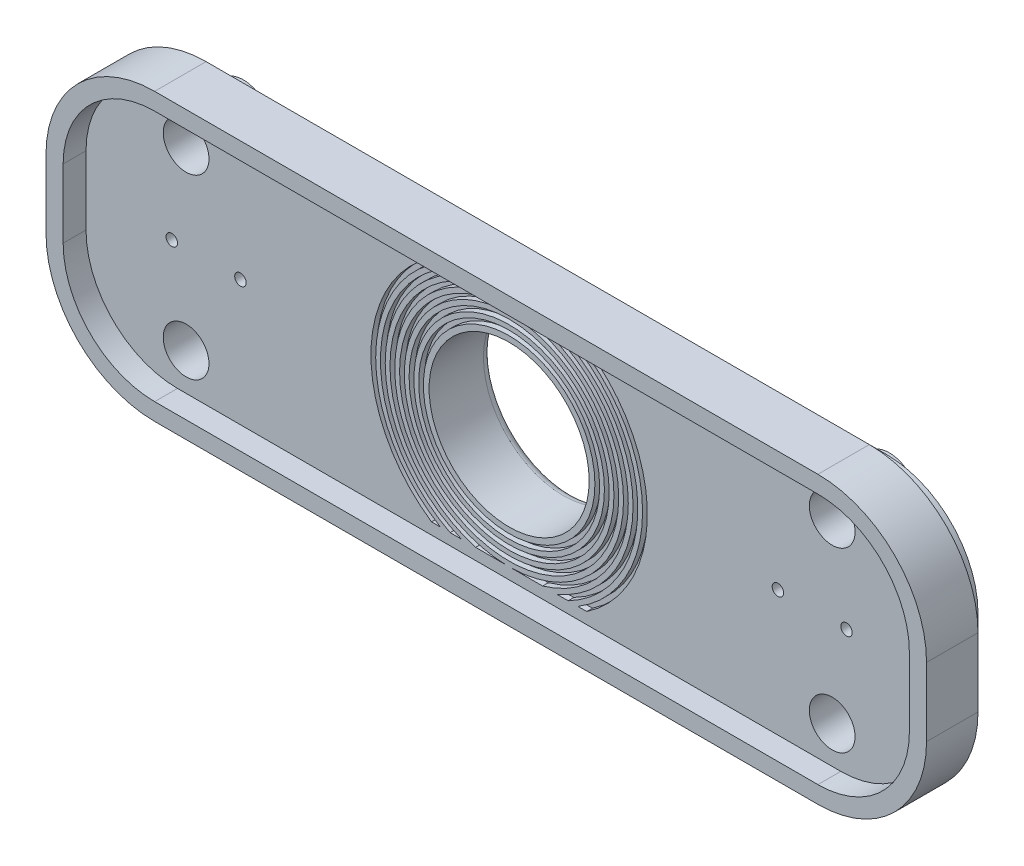
SolidWorks part; units mm, degrees
ref_plane "Front Plane" through (0, 0, 0) normal (0, 0, 1) x (1, 0, 0)
ref_plane "Top Plane" through (0, 0, 0) normal (0, 1, 0) x (1, 0, 0)
ref_plane "Right Plane" through (0, 0, 0) normal (1, 0, 0) x (0, 0, -1)
sketch "Sketch1" plane through (0, 0, 0) normal (0, 0, 1) x (1, 0, 0)
  line L0 (-29, 12.5) -> (29, 12.5)
  line L1 (-29, 11) -> (29, 11)
  line L2 (-37, 3) -> (-37, -3)
  line L3 (-29, -11) -> (29, -11)
  line L4 (37, 3) -> (37, -3)
  line L5 (38.5, 3) -> (38.5, -3)
  line L6 (-29, -12.5) -> (29, -12.5)
  line L7 (-38.5, 3) -> (-38.5, -3)
  arc A0 (29, -11) -> (37, -3) centre (29, -3) ccw
  arc A1 (29, 11) -> (37, 3) centre (29, 3) cw
  arc A2 (-37, -3) -> (-29, -11) centre (-29, -3) ccw
  arc A3 (-29, 11) -> (-37, 3) centre (-29, 3) ccw
  arc A4 (29, 12.5) -> (38.5, 3) centre (29, 3) cw
  arc A5 (29, -12.5) -> (38.5, -3) centre (29, -3) ccw
  arc A6 (-38.5, -3) -> (-29, -12.5) centre (-29, -3) ccw
  arc A7 (-29, 12.5) -> (-38.5, 3) centre (-29, 3) ccw
  point P4 (0, 11)
  point P6 (37, 0)
  point P9 (37, -11)
  point P12 (37, 11)
  dimension "D3" = 8
  dimension "D1" = 74
  dimension "D2" = 22
  dimension "D4" = 1.5
extrude "Boss-Extrude1" add sketch "Sketch1" along normal mid plane 2 contours L2 A2 L3 A0 L4 A1 L1 A3
extrude "Boss-Extrude2" add sketch "Sketch1<4>" along normal blind 3 and the other way blind 1.5
sketch "Sketch1<4>" plane through (0, 0, 0) normal (0, 0, 1) x (1, 0, 0) same geometry as "Sketch1"
sketch "Sketch2" plane through (0, 0, -1) normal (0, 0, -1) x (-1, 0, 0)
  line L0 (29, 10) -> (-29, 10)
  line L1 (-36, 3) -> (-36, -3)
  line L2 (-29, -10) -> (29, -10)
  line L3 (36, -3) -> (36, 3)
  line L4 (29, 11) -> (-29, 11)
  line L5 (-37, 3) -> (-37, -3)
  line L6 (-29, -11) -> (29, -11)
  line L7 (37, -3) -> (37, 3)
  line L8 (29, 11) -> (-29, 11)
  line L9 (-37, 3) -> (-37, -3)
  line L10 (-29, -11) -> (29, -11)
  line L11 (37, -3) -> (37, 3)
  arc A0 (-29, 10) -> (-36, 3) centre (-29, 3) ccw
  arc A1 (-36, -3) -> (-29, -10) centre (-29, -3) ccw
  arc A2 (29, -10) -> (36, -3) centre (29, -3) ccw
  arc A3 (36, 3) -> (29, 10) centre (29, 3) ccw
  arc A4 (37, 3) -> (29, 11) centre (29, 3) ccw
  arc A5 (-29, 11) -> (-37, 3) centre (-29, 3) ccw
  arc A6 (-37, -3) -> (-29, -11) centre (-29, -3) ccw
  arc A7 (29, -11) -> (37, -3) centre (29, -3) ccw
  arc A8 (37, 3) -> (29, 11) centre (29, 3) ccw
  arc A9 (-29, 11) -> (-37, 3) centre (-29, 3) ccw
  arc A10 (-37, -3) -> (-29, -11) centre (-29, -3) ccw
  arc A11 (29, -11) -> (37, -3) centre (29, -3) ccw
  dimension "D1" = 0
  dimension "D2" = 1
extrude "Boss-Extrude3" add sketch "Sketch2" along normal blind 2
sketch "Sketch3" plane through (0, 0, 1) normal (0, 0, 1) x (1, 0, 0)
  line L0 (-28.25, 0) -> (28.25, 0) construction
  line L1 (-28.25, 7.75) -> (-28.25, -7.75) construction
  line L2 (28.25, 7.75) -> (28.25, -7.75) construction
  line L3 (-28.25, 0) -> (-29.5, 0) construction
  line L4 (28.25, 0) -> (29.5, 0) construction
  line L5 (0, 11) -> (0, -11) construction
  line L6 (-29, -11) -> (29, -11) construction
  circle A0 centre (0, 0) radius 7
  circle A1 centre (-28.25, 7.75) radius 2
  circle A2 centre (28.25, 7.75) radius 2
  circle A3 centre (28.25, -7.75) radius 2
  circle A4 centre (-28.25, -7.75) radius 2
  circle A5 centre (-29.5, 0) radius 0.5
  circle A6 centre (29.5, 0) radius 0.5
  circle A7 centre (23.5, 0) radius 0.5
  circle A8 centre (-23.5, 0) radius 0.5
  point P6 (0, 0)
  point P9 (-28.25, 0)
  point P12 (28.25, 0)
  point P28 (0, 0)
  dimension "D1" = 14
  dimension "D2" = 4
  dimension "D3" = 56.5
  dimension "D4" = 15.5
  dimension "D5" = 1
  dimension "D6" = 58
  dimension "D7" = 46
extrude "Cut-Extrude1" cut sketch "Sketch3" against normal through all
sketch "Sketch4" plane through (0, 0, -1) normal (0, 0, -1) x (-1, 0, 0)
  circle A0 centre (0, 0) radius 7 construction
  circle A1 centre (0, 0) radius 7
  circle A2 centre (0, 0) radius 8.5
  dimension "D1" = 17
extrude "Boss-Extrude4" add sketch "Sketch4" along normal blind 3.5
sketch "Sketch5" plane through (0, 0, -1) normal (0, 0, -1) x (-1, 0, 0)
  circle A0 centre (29.5, 0) radius 4.25
  circle A1 centre (-29.5, 0) radius 4.25
  circle A2 centre (-29.5, 0) radius 3.1
  circle A3 centre (29.5, 0) radius 3.1
  dimension "D1" = 8.5
  dimension "D2" = 6.2
extrude "Boss-Extrude5" add sketch "Sketch5" along normal blind 3.9
sketch "Sketch6" plane through (0, 0, -1) normal (0, 0, -1) x (-1, 0, 0)
  circle A0 centre (23.5, 0) radius 2.5
  circle A3 centre (-23.5, 0) radius 2.5
  circle A4 centre (-23.5, 0) radius 1.6
  circle A5 centre (23.5, 0) radius 1.6
  dimension "D1" = 5
  dimension "D2" = 3.2
extrude "Boss-Extrude6" add sketch "Sketch6" along normal blind 4.5
sketch "Sketch7" plane through (0, 0, -1) normal (0, 0, -1) x (-1, 0, 0)
  circle A0 centre (-28.25, 7.75) radius 2.5
  circle A1 centre (-28.25, 7.75) radius 2 construction
  circle A2 centre (-28.25, 7.75) radius 2
  circle A3 centre (28.25, 7.75) radius 2 construction
  circle A4 centre (28.25, -7.75) radius 2 construction
  circle A5 centre (-28.25, -7.75) radius 2 construction
  circle A6 centre (28.25, 7.75) radius 2
  circle A7 centre (28.25, -7.75) radius 2
  circle A8 centre (-28.25, -7.75) radius 2
  circle A9 centre (-28.25, -7.75) radius 2.5
  circle A10 centre (28.25, 7.75) radius 2.5
  circle A11 centre (28.25, -7.75) radius 2.5
  dimension "D1" = 5
extrude "Boss-Extrude7" add sketch "Sketch7" along normal blind 3
fillet "Fillet1" radius 0.75 1 edges at (-7, 0, -4.5)
chamfer "Chamfer1" distance 0.75 angle 45 4 edges at (-23, 0, -1) (24, 0, -1) (30, 0, -1) (-29, 0, -1)
chamfer "Chamfer2" distance 0.6 angle 45 2 edges at (-25.1, 0, -5.5) (21.9, 0, -5.5)
sketch "Sketch8" plane through (0, 0, 1) normal (0, 0, 1) x (1, 0, 0)
  line L1 (0, 10) -> (0, -10) construction
  line L2 (-7.5, 10) -> (7.5, 10)
  line L3 (-7.5, -10) -> (7.5, -10)
  line L4 (-29, 11) -> (29, 11) construction
  arc A0 (7.5, -10) -> (7.5, 10) centre (0, 0) ccw
  arc A1 (-7.5, 10) -> (-7.5, -10) centre (0, 0) ccw
  circle A2 centre (0, 0) radius 7.5
  circle A3 centre (0, 0) radius 7.9167
  circle A4 centre (0, 0) radius 8.3333
  circle A5 centre (0, 0) radius 8.75
  circle A6 centre (0, 0) radius 9.1667
  circle A7 centre (0, 0) radius 9.5833
  circle A8 centre (0, 0) radius 10.0033
  arc A9 (-2.9285, 10) -> (-2.9285, -10) centre (0, 0) ccw
  arc A10 (-4.1753, 10) -> (-4.1753, -10) centre (0, 0) ccw
  arc A11 (-5.1612, 10) -> (-5.1612, -10) centre (0, 0) ccw
  arc A12 (-6.0157, 10) -> (-6.0157, -10) centre (0, 0) ccw
  arc A13 (-6.7888, 10) -> (-6.7888, -10) centre (0, 0) ccw
  circle A14 centre (0, 0) radius 12.0867 construction
  circle A15 centre (0, 0) radius 11.67 construction
  circle A16 centre (0, 0) radius 11.2533 construction
  circle A17 centre (0, 0) radius 10.8367 construction
  circle A18 centre (0, 0) radius 10.42 construction
  arc A19 (6.7888, -10) -> (6.7888, 10) centre (0, 0) ccw
  arc A20 (6.0157, -10) -> (6.0157, 10) centre (0, 0) ccw
  arc A21 (5.1612, -10) -> (5.1612, 10) centre (0, 0) ccw
  arc A22 (4.1753, -10) -> (4.1753, 10) centre (0, 0) ccw
  arc A23 (2.9285, -10) -> (2.9285, 10) centre (0, 0) ccw
  point P3 (0, 0)
  point P9 (0, 10)
  point P12 (0, -10)
  dimension "D1" = 25
  dimension "D3" = 15
  dimension "D4" = 0.4167
  dimension "D2" = 1
  dimension "D5" = 0.4167
  dimension "D6" = 0.4167
  dimension "D7" = 0.4167
  dimension "D8" = 0.4167
  dimension "D9" = 0.42
  dimension "D10" = 0.4167
  dimension "D11" = 0.4167
  dimension "D12" = 0.4167
  dimension "D13" = 0.4167
  dimension "D14" = 0.4167
extrude "Cut-Extrude6" cut sketch "Sketch8" against normal blind 0.5 contours A3 A2 | A5 A4 | A7 A6 | L2 A9 L3 A8 | L2 A11 L3 A10 | L2 A13 L3 A12 | L3 A23 L2 A8 | A22 L3 A21 L2 | A20 L3 A19 L2 region at (-6.4022, 9.791, 1) region at (-4.6682, 9.7878, 1) region at (-1.5934, 9.9776, 1) region at (1.5934, 9.9776, 1) region at (4.6682, 9.7878, 1) region at (6.4022, 9.791, 1) region at (-7.6927, 0, 1) region at (-8.5025, 0, 1) region at (-9.3123, 0, 1)
